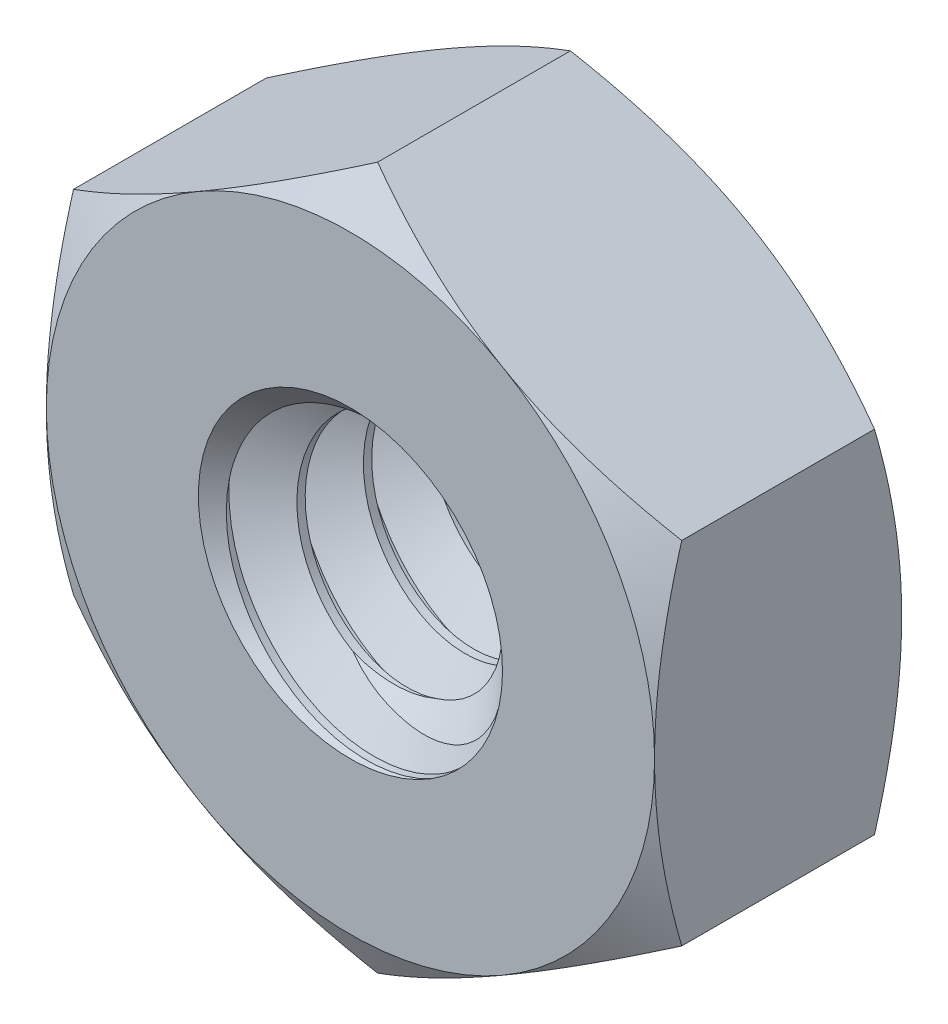
SolidWorks part; units mm, degrees
material "AISI Type 316L stainless steel"
ref_plane "Front" through (0, 0, 0) normal (0, 0, 1) x (1, 0, 0)
ref_plane "Top" through (0, 0, 0) normal (0, 1, 0) x (1, 0, 0)
ref_plane "Right" through (0, 0, 0) normal (1, 0, 0) x (0, 0, -1)
sketch "Sketch1" plane through (0, 0, 0) normal (0, 0, 1) x (1, 0, 0)
  line L1 (-1.6, 0.9238) -> (-1.6, -0.9238)
  line L2 (-1.6, -0.9238) -> (0, -1.8475)
  line L3 (0, -1.8475) -> (1.6, -0.9238)
  line L4 (1.6, -0.9238) -> (1.6, 0.9238)
  line L5 (1.6, 0.9238) -> (0, 1.8475)
  line L6 (0, 1.8475) -> (-1.6, 0.9238)
  circle A0 centre (0, 0) radius 1.6 construction
  circle A1 centre (0, 0) radius 0.8 construction
  point P10 (0, 0.8)
  dimension "hex" = 3.2
  dimension "dia" = 1.6
extrude "Extrude1" add sketch "Sketch1" along normal mid plane 1.3
sketch "Sketch4" plane through (0, 0, -0.65) normal (0, 0, -1) x (-1, 0, 0)
  circle A0 centre (0, 0) radius 0.8 construction
  circle A1 centre (0, 0) radius 0.8
sketch "Sketch10" plane through (0, 0, 0.65) normal (0, 0, 1) x (1, 0, 0)
  circle A0 centre (0, 0) radius 0.8 construction
  circle A1 centre (0, 0) radius 0.8
extrude "Cut-Extrude2" cut sketch "Sketch10" against normal through all draft 45
sketch "Sketch11" plane through (0, 0, -0.65) normal (0, 0, -1) x (-1, 0, 0)
  circle A0 centre (0, 0) radius 0.8 construction
  circle A1 centre (0, 0) radius 0.8
extrude "Cut-Extrude3" cut sketch "Sketch11" against normal through all draft 45
sketch "Sketch13" plane through (0, 0, -0.65) normal (0, 0, -1) x (-1, 0, 0)
  circle A0 centre (0, 0) radius 0.8 construction
  circle A1 centre (0, 0) radius 0.8
extrude "Boss-Extrude1" add sketch "Sketch13" against normal up to vertex (1.3 mm away) separate body up to point (-1.6, 0.9238, 0.65)
curve "Helix/Spiral3" pitch 0.35 height 1.3 radius 0.8 centre (0, 0, -0.65) axis (0, 0, 1) start towards (0, 1, 0)
sketch "Sketch12" plane through (0, 0, 0) normal (1, 0, 0) x (0, 0, -1)
  line L0 (0.9563, 0.8) -> (0.65, 0.8)
  line L1 (0.9563, 0.8) -> (0.825, 0.5727)
  line L2 (0.825, 0.5727) -> (0.7812, 0.5727)
  line L3 (0.7812, 0.5727) -> (0.65, 0.8)
  line L4 (0.8031, 0.5727) -> (0.8031, 0.8) construction
  line L5 (0.7156, 0.6863) -> (0.8906, 0.6863) construction
  dimension "D1" = 60
  dimension "D2" = 0.0437
  dimension "D3" = 0.175
sweep "Cut-Sweep1" cut profiles "Sketch12" path "Helix/Spiral3" align with end faces yes
combine bodies "Combine1" operation type subtract main body 116 bodies to subtract 118
sketch "Sketch7" plane through (0, 0, 0.65) normal (0, 0, 1) x (1, 0, 0)
  circle A0 centre (0, 0) radius 1.6 construction
  circle A1 centre (0, 0) radius 1.6
extrude "Extrude2" cut sketch "Sketch7" against normal blind 25.4 draft 60 flip side to cut
mirror "Mirror2" about plane through (0, 0, 0) normal (0, 0, 1) of "Extrude2"
sketch "Sketch8" plane through (0, 0, 0.65) normal (0, 0, 1) x (1, 0, 0)
  line L0 (-0.5657, 0.5657) -> (0, 0) construction
  line L1 (0, -0.6275) -> (0, 0.6275) construction
  circle A1 centre (0, 0) radius 0.8 construction
  point P0 (-0.5657, 0.5657)
  dimension "D1" = 45
sketch "Sketch14" plane through (0, 0, 0.65) normal (0, 0, 1) x (1, 0, 0)
  line L0 (0, 0) -> (-0.8, 0) construction
  arc A0 (0.4245, -0.6781) -> (0.7814, -0.1714) centre (0, 0) ccw construction
equation "\"D3@Helix/Spiral3\" = \"length@Extrude1\" "
equation "\"D2@Sketch12\" = \"D4@Helix/Spiral3\"*.125"
equation "\"D3@Sketch12\" = \"D4@Helix/Spiral3\"*.50"
